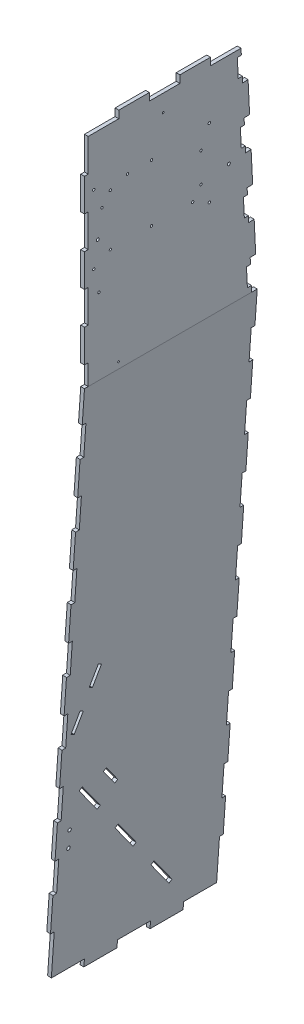
SolidWorks part; units mm, degrees
ref_plane "Front Plane" through (0, 0, 0) normal (0, 0, 1) x (1, 0, 0)
ref_plane "Top Plane" through (0, 0, 0) normal (0, 1, 0) x (1, 0, 0)
ref_plane "Right Plane" through (0, 0, 0) normal (1, 0, 0) x (0, 0, -1)
sketch "Sketch1" plane through (0, 0, 0) normal (0, 0, 1) x (1, 0, 0)
  line L0 (-215.8818, 2052.32) -> (-215.8818, 1463.04)
  line L1 (-215.8818, 1463.04) -> (-316.0886, 20.32)
  line L2 (-316.0886, 20.32) -> (-317.5, 0)
  line L4 (-215.8818, 2052.32) -> (-215.8818, 2072.64)
  line L6 (-215.8818, 2072.64) -> (-205.7153, 2072.64)
  line L7 (-205.7153, 2072.64) -> (-205.7153, 1463.04)
  line L8 (-205.7153, 1463.04) -> (-307.3335, 0)
  line L9 (-317.5, 0) -> (-307.3335, 0)
  line L10 (-371.5407, 0) -> (-280.9748, 0) construction
  line L13 (-371.5407, 20.32) -> (-280.9748, 20.32) construction
  line L15 (-205.7153, 1463.04) -> (205.7153, 1463.04) construction
  point P23 (-305.9221, 20.32)
  dimension "D1" = 307.3335
extrude "Boss-Extrude1" add sketch "Sketch1" against normal blind 469.9
sketch "Sketch2" plane through (-315.9757, 21.9467, 0) normal (-0.9976, 0.0693, 0) x (0, 0, 1)
  line L35 (0, 1355.6785) -> (0, 0.1049)
  line L37 (-234.95, 1444.5652) -> (-234.95, -21.9996) construction
  line L40 (-10.16, 0.1049) -> (0, 0.1049)
  line L43 (-10.16, 0.1049) -> (-10.16, -21.9996)
  line L46 (0, 1272.0274) -> (-10.16, 1272.0274)
  line L47 (-10.16, 1355.6785) -> (-10.16, 1272.0274)
  line L48 (0, 1355.6785) -> (-10.16, 1355.6785)
  line L49 (0, 1177.9051) -> (-10.16, 1177.9051)
  line L50 (-10.16, 1177.9051) -> (-10.16, 1094.2274)
  line L51 (0, 1094.2274) -> (-10.16, 1094.2274)
  line L52 (0, 916.4274) -> (-10.16, 916.4274)
  line L53 (-10.16, 1000.1317) -> (-10.16, 916.4274)
  line L54 (0, 1000.1317) -> (-10.16, 1000.1317)
  line L55 (0, 822.3583) -> (-10.16, 822.3583)
  line L56 (0, 738.6274) -> (-10.16, 738.6274)
  line L57 (-10.16, 822.3583) -> (-10.16, 738.6274)
  line L58 (0, 644.5849) -> (-10.16, 644.5849)
  line L59 (-10.16, 644.5849) -> (-10.16, 560.8274)
  line L60 (0, 560.8274) -> (-10.16, 560.8274)
  line L61 (0, 466.8115) -> (-10.16, 466.8115)
  line L62 (-10.16, 466.8115) -> (-10.16, 383.0274)
  line L63 (0, 383.0274) -> (-10.16, 383.0274)
  line L64 (0, 289.0381) -> (-10.16, 289.0381)
  line L65 (-10.16, 289.0381) -> (-10.16, 205.2274)
  line L66 (0, 205.2274) -> (-10.16, 205.2274)
  line L67 (0, 111.2647) -> (-10.16, 111.2647)
  line L68 (-10.16, 111.2647) -> (-10.16, 0.1049)
  line L69 (0, 0.1049) -> (-10.16, 0.1049)
  line L70 (-10.16, -21.9996) -> (0, -21.9996)
  line L71 (0, 0.1049) -> (0, -21.9996)
  line L72 (-469.9, 1444.5652) -> (0, 1444.5652) construction
  line L73 (-469.9, -21.9996) -> (0, -21.9996) construction
  line L74 (-469.9, 0.1049) -> (-469.9, -21.9996)
  line L75 (-459.74, -21.9996) -> (-469.9, -21.9996)
  line L76 (-469.9, 0.1049) -> (-459.74, 0.1049)
  line L77 (-459.74, 111.2647) -> (-459.74, 0.1049)
  line L78 (-469.9, 111.2647) -> (-459.74, 111.2647)
  line L79 (-469.9, 205.2274) -> (-459.74, 205.2274)
  line L80 (-459.74, 289.0381) -> (-459.74, 205.2274)
  line L81 (-469.9, 289.0381) -> (-459.74, 289.0381)
  line L82 (-469.9, 383.0274) -> (-459.74, 383.0274)
  line L83 (-459.74, 466.8115) -> (-459.74, 383.0274)
  line L84 (-469.9, 466.8115) -> (-459.74, 466.8115)
  line L85 (-469.9, 560.8274) -> (-459.74, 560.8274)
  line L86 (-459.74, 644.5849) -> (-459.74, 560.8274)
  line L87 (-469.9, 644.5849) -> (-459.74, 644.5849)
  line L88 (-459.74, 822.3583) -> (-459.74, 738.6274)
  line L89 (-469.9, 738.6274) -> (-459.74, 738.6274)
  line L90 (-469.9, 822.3583) -> (-459.74, 822.3583)
  line L91 (-469.9, 1000.1317) -> (-459.74, 1000.1317)
  line L92 (-459.74, 1000.1317) -> (-459.74, 916.4274)
  line L93 (-469.9, 916.4274) -> (-459.74, 916.4274)
  line L94 (-469.9, 1094.2274) -> (-459.74, 1094.2274)
  line L95 (-459.74, 1177.9051) -> (-459.74, 1094.2274)
  line L96 (-469.9, 1177.9051) -> (-459.74, 1177.9051)
  line L97 (-469.9, 1355.6785) -> (-459.74, 1355.6785)
  line L98 (-459.74, 1355.6785) -> (-459.74, 1272.0274)
  line L99 (-469.9, 1272.0274) -> (-459.74, 1272.0274)
  line L100 (-459.74, 0.1049) -> (-459.74, -21.9996)
  line L101 (-459.74, 0.1049) -> (-469.9, 0.1049)
  line L102 (-469.9, 1355.6785) -> (-469.9, 0.1049)
  line L103 (-469.9, 1444.5652) -> (-469.9, -21.9996) construction
  line L104 (-459.74, 205.2274) -> (-469.9, 205.2274) construction
  line M1 (0, -21.9996) -> (0, 1444.5652)
  line M3 (-469.9, 1444.5652) -> (-469.9, -21.9996)
  line M4 (-469.9, -21.9996) -> (0, -21.9996)
extrude "Cut-Extrude1" cut sketch "Sketch2" against normal blind 10.16 contours L66 L35 L64 L65 | L69 L67 L68 M1 | L60 L35 L58 L59 | L63 L35 L61 L62 | L55 L57 L56 L35 | L35 L54 L53 L52 | L51 L35 L49 L50 | L35 L48 L47 L46 | L40 L43 M4 M1 | L100 L76 M3 M4 | L78 L76 L77 M3 | L81 L79 L80 M3 | L84 L82 L83 M3 | L87 L85 L86 M3 | L90 L89 L88 M3 | L93 L92 L91 M3 | L96 L94 L95 M3 | L99 L98 L97 M3 region at (-224.9388, 1332.6419, -464.82) region at (-237.2577, 1155.2825, -464.82) region at (-249.5765, 977.9231, -464.82) region at (-261.8953, 800.5637, -464.82) region at (-274.2142, 623.2043, -464.82) region at (-286.533, 445.8449, -464.82) region at (-298.8518, 268.4855, -464.82) region at (-316.7342, 11.0257, -464.82) region at (-312.1173, 77.4977, -5.08) region at (-298.8518, 268.4855, -5.08) region at (-286.533, 445.8449, -5.08) region at (-274.2142, 623.2043, -5.08) region at (-261.8953, 800.5637, -5.08) region at (-249.5765, 977.9231, -5.08) region at (-237.2577, 1155.2825, -5.08) region at (-224.9388, 1332.6419, -5.08) region at (-316.7342, 11.0257, -5.08) region at (-312.1173, 77.4977, -464.82)
sketch "Sketch3" plane through (-215.8818, 0, 0) normal (-1, 0, 0) x (0, 0, 1)
  line L0 (0, 2052.32) -> (-10.16, 2052.32) construction
  line L1 (0, 1963.42) -> (-10.16, 1963.42) construction
  line L2 (-10.16, 2052.32) -> (-10.16, 1963.42) construction
  line L3 (0, 1874.52) -> (-10.16, 1874.52) construction
  line L4 (0, 1463.04) -> (0, 2072.64)
  line L5 (0, 2072.64) -> (-469.9, 2072.64)
  line L6 (-469.9, 2072.64) -> (-469.9, 1463.04)
  line L8 (0, 1463.04) -> (0, 2072.64)
  line L9 (0, 2072.64) -> (-469.9, 2072.64)
  line L12 (0, 1785.62) -> (-10.16, 1785.62) construction
  line L13 (-10.16, 1874.52) -> (-10.16, 1785.62) construction
  line L14 (0, 1696.72) -> (-10.16, 1696.72) construction
  line L15 (0, 1607.82) -> (-10.16, 1607.82) construction
  line L16 (-10.16, 1696.72) -> (-10.16, 1607.82) construction
  line L17 (0, 1518.92) -> (-10.16, 1518.92) construction
  line L18 (-10.16, 1518.92) -> (-10.16, 1488.44) construction
  line L19 (0, 2052.32) -> (-10.16, 2052.32)
  line L20 (0, 1963.42) -> (-10.16, 1963.42)
  line L21 (-10.16, 2052.32) -> (-10.16, 1963.42)
  line L22 (0, 1874.52) -> (-10.16, 1874.52)
  line L23 (0, 1785.62) -> (-10.16, 1785.62)
  line L24 (-10.16, 1874.52) -> (-10.16, 1785.62)
  line L25 (0, 1696.72) -> (-10.16, 1696.72)
  line L26 (0, 1607.82) -> (-10.16, 1607.82)
  line L27 (-10.16, 1696.72) -> (-10.16, 1607.82)
  line L28 (0, 1518.92) -> (-10.16, 1518.92)
  line L29 (-10.16, 1518.92) -> (-10.16, 1488.44)
  line L30 (0, 2052.32) -> (0, 1463.04)
  line L31 (-234.95, 1463.04) -> (-234.95, 2072.64) construction
  line L32 (-10.16, 2052.32) -> (0, 2052.32)
  line L33 (-10.16, 2052.32) -> (-10.16, 2072.64)
  line L34 (-10.16, 2072.64) -> (0, 2072.64)
  line L35 (0, 2052.32) -> (0, 2072.64)
  line L36 (-469.9, 1463.04) -> (-439.9, 2072.64)
  line L37 (-469.9, 1463.04) -> (-465.752, 1547.3282)
  line L38 (-469.9, 1463.04) -> (-454.9181, 1462.3027)
  line L39 (-465.752, 1547.3282) -> (-450.7701, 1546.5909)
  line L40 (-454.9181, 1462.3027) -> (-450.7701, 1546.5909)
  line L41 (-465.752, 1547.3282) -> (-450.7701, 1546.5909)
  line L42 (-465.752, 1547.3282) -> (-461.6039, 1631.6164)
  line L43 (-450.7701, 1546.5909) -> (-446.622, 1630.8791)
  line L44 (-461.6039, 1631.6164) -> (-446.622, 1630.8791)
  line L45 (-461.6039, 1631.6164) -> (-446.622, 1630.8791)
  line L46 (-461.6039, 1631.6164) -> (-457.4559, 1715.9046)
  line L47 (-446.622, 1630.8791) -> (-442.474, 1715.1673)
  line L48 (-457.4559, 1715.9046) -> (-442.474, 1715.1673)
  line L49 (-457.4559, 1715.9046) -> (-442.474, 1715.1673)
  line L50 (-457.4559, 1715.9046) -> (-453.3078, 1800.1927)
  line L51 (-442.474, 1715.1673) -> (-438.326, 1799.4554)
  line L52 (-453.3078, 1800.1927) -> (-438.326, 1799.4554)
  line L53 (-453.3078, 1800.1927) -> (-438.326, 1799.4554)
  line L54 (-10.16, 1488.44) -> (-10.16, 1463.04)
  line L56 (-453.3078, 1800.1927) -> (-449.1598, 1884.4809)
  line L57 (-438.326, 1799.4554) -> (-434.1779, 1883.7436)
  line L58 (-449.1598, 1884.4809) -> (-434.1779, 1883.7436)
  line L59 (-449.1598, 1884.4809) -> (-434.1779, 1883.7436)
  line L60 (-449.1598, 1884.4809) -> (-445.0118, 1968.7691)
  line L61 (-434.1779, 1883.7436) -> (-430.0299, 1968.0318)
  line L62 (-445.0118, 1968.7691) -> (-430.0299, 1968.0318)
  line L63 (-10.16, 2052.32) -> (-469.9, 2052.32) construction
  line L64 (-469.9, 2072.64) -> (-469.9, 1463.04) construction
  line L65 (-445.0118, 1968.7691) -> (-430.0299, 1968.0318)
  line L66 (-445.0118, 1968.7691) -> (-440.8637, 2053.0573)
  line L67 (-430.0299, 1968.0318) -> (-425.8818, 2052.32)
  line L68 (-440.8637, 2053.0573) -> (-425.8818, 2052.32)
  line L69 (-425.8818, 2052.32) -> (-440.9, 2052.32)
  line L70 (-440.8637, 2053.0573) -> (-425.8818, 2052.32)
  line L71 (-440.8637, 2053.0573) -> (-439.4854, 2081.0647)
  line L72 (-425.8818, 2052.32) -> (-424.5035, 2080.3274)
  line L73 (-439.4854, 2081.0647) -> (-424.5035, 2080.3274)
  line L74 (-469.9, 1463.04) -> (0, 1463.04) construction
  line L78 (-469.9, 1463.04) -> (0, 1463.04)
  line L79 (-469.9, 1463.04) -> (0, 1463.04)
  line M7 (0, 1463.04) -> (0, 2072.64)
  line M8 (0, 2072.64) -> (-469.9, 2072.64)
  line M9 (-469.9, 2072.64) -> (-469.9, 1463.04)
  line M10 (-469.9, 1463.04) -> (0, 1463.04)
  dimension "D2" = 30
  dimension "D3" = 15
  dimension "D1" = 0
extrude "Cut-Extrude2" cut sketch "Sketch3" against normal blind 12.7 contours M10 | L29 L54 L28 M10 M7 | L36 L66 M9 M8 | L48 L36 L44 L47 | L58 L36 L52 L57 | L67 L69 L36 L62 | L25 L27 L26 L8 | L22 L24 L23 L8 | L19 L21 L20 L8 | L33 L19 L8 M8 | L68 L72 L36 M8 | L69 L68 L66 region at (-215.8818, 1490.98, -5.08) region at (-215.8818, 1652.27, -5.08) region at (-215.8818, 1505, -460.337) region at (-215.8818, 1869.44, -459.9) region at (-215.8818, 1830.07, -5.08) region at (-215.8818, 1673.3918, -452.039) region at (-215.8818, 2062.6632, -432.8357) region at (-215.8818, 2007.87, -5.08) region at (-215.8818, 1841.9682, -443.7429) region at (-215.8818, 2052.5658, -435.8819) region at (-215.8818, 2062.48, -5.08) region at (-215.8818, 2010.36, -435.4449)
sketch "Sketch4" plane through (-215.8818, 0, 0) normal (-1, 0, 0) x (0, 0, 1)
  line L1 (-425.8818, 2072.64) -> (-342.7375, 2072.64)
  line L2 (-425.8818, 2072.64) -> (-425.8818, 2052.32)
  line L3 (-425.8818, 2052.32) -> (-342.7375, 2052.32)
  line L4 (-342.7375, 2072.64) -> (-342.7375, 2052.32)
  line L5 (-10.16, 2072.64) -> (-10.16, 1963.42) construction
  line L6 (-342.7375, 2072.64) -> (-259.5931, 2072.64)
  line L7 (-342.7375, 2072.64) -> (-342.7375, 2052.32)
  line L8 (-342.7375, 2052.32) -> (-259.5931, 2052.32)
  line L9 (-259.5931, 2072.64) -> (-259.5931, 2052.32)
  line L10 (-259.5931, 2072.64) -> (-176.4487, 2072.64)
  line L11 (-259.5931, 2072.64) -> (-259.5931, 2052.32)
  line L12 (-259.5931, 2052.32) -> (-176.4487, 2052.32)
  line L13 (-176.4487, 2072.64) -> (-176.4487, 2052.32)
  line L14 (-176.4487, 2072.64) -> (-93.3044, 2072.64)
  line L15 (-176.4487, 2072.64) -> (-176.4487, 2052.32)
  line L16 (-176.4487, 2052.32) -> (-93.3044, 2052.32)
  line L17 (-93.3044, 2072.64) -> (-93.3044, 2052.32)
  line L18 (-93.3044, 2072.64) -> (-10.16, 2072.64)
  line L19 (-93.3044, 2072.64) -> (-93.3044, 2052.32)
  line L20 (-93.3044, 2052.32) -> (-10.16, 2052.32)
  line L21 (-10.16, 2072.64) -> (-10.16, 2052.32)
  line L23 (-430.0299, 1968.0318) -> (-424.8818, 2072.64) construction
  line L24 (-424.8818, 2072.64) -> (-10.16, 2072.64) construction
  line M26 (-10.16, 1963.42) -> (-10.16, 2072.64)
  line M27 (-10.16, 2072.64) -> (-424.8818, 2072.64)
  dimension "D1" = 20.32
extrude "Cut-Extrude3" cut sketch "Sketch4" against normal blind 12.7 contours L4 L3 M27 | L13 L9 L12 M27 | L17 L20 M26 M27 region at (-215.8818, 2062.48, -384.3097) region at (-215.8818, 2062.48, -218.0209) region at (-215.8818, 2062.48, -51.7322)
sketch "Sketch5" plane through (-315.9757, 21.9467, 0) normal (-0.9976, 0.0693, 0) x (0, 0, 1)
  line L1 (-459.74, -21.9996) -> (-369.824, -21.9996)
  line L2 (-459.74, -21.9996) -> (-459.74, -1.6796)
  line L3 (-459.74, -1.6796) -> (-369.824, -1.6796)
  line L4 (-369.824, -21.9996) -> (-369.824, -1.6796)
  line L5 (-369.824, -21.9996) -> (-279.908, -21.9996)
  line L6 (-369.824, -21.9996) -> (-369.824, -1.6796)
  line L7 (-369.824, -1.6796) -> (-279.908, -1.6796)
  line L8 (-279.908, -21.9996) -> (-279.908, -1.6796)
  line L9 (-279.908, -21.9996) -> (-189.992, -21.9996)
  line L10 (-279.908, -21.9996) -> (-279.908, -1.6796)
  line L11 (-279.908, -1.6796) -> (-189.992, -1.6796)
  line L12 (-189.992, -21.9996) -> (-189.992, -1.6796)
  line L13 (-189.992, -21.9996) -> (-100.076, -21.9996)
  line L14 (-189.992, -21.9996) -> (-189.992, -1.6796)
  line L15 (-189.992, -1.6796) -> (-100.076, -1.6796)
  line L16 (-100.076, -21.9996) -> (-100.076, -1.6796)
  line L17 (-100.076, -21.9996) -> (-10.16, -21.9996)
  line L18 (-100.076, -21.9996) -> (-100.076, -1.6796)
  line L19 (-100.076, -1.6796) -> (-10.16, -1.6796)
  line L20 (-10.16, -21.9996) -> (-10.16, -1.6796)
  line L21 (-10.16, 111.2647) -> (-10.16, -21.9996) construction
  dimension "D1" = 20.32
extrude "Cut-Extrude4" cut sketch "Sketch5" against normal blind 12.7 contours L1 L4 L3 L2 | L9 L12 L11 L8 | L17 L20 L19 L18 L16 region at (-316.796, 10.1356, -414.782) region at (-316.796, 10.1356, -234.95) region at (-316.796, 10.1356, -55.118)
sketch "Sketch6" plane through (-315.9757, 21.9467, 0) normal (-0.9976, 0.0693, 0) x (0, 0, 1)
  line L0 (-217.3726, 211.9965) -> (-163.4402, 285.2141)
  line L1 (-325.2304, 65.5562) -> (-271.298, 138.7738)
  line L2 (-44.1085, 632.6765) -> (-22.5289, 586.4358) construction
  line L3 (-74.8989, 674.6188) -> (-65.6881, 678.9173) construction
  line L8 (-271.6486, 139.032) -> (-279.8219, 145.0526) construction
  line L56 (-87.2678, 725.158) -> (-65.6881, 678.9173) construction
  line L57 (-74.8989, 674.6188) -> (-96.4785, 720.8595) construction
  line L58 (-31.7396, 582.1373) -> (-22.5289, 586.4358) construction
  line L59 (-31.7396, 582.1373) -> (-53.3192, 628.3781) construction
  line L60 (-53.3192, 628.3781) -> (-44.1085, 632.6765) construction
  line L63 (-117.6881, 364.4573) -> (-63.7557, 437.6749) construction
  line L65 (-225.5528, 218.0222) -> (-171.6205, 291.2397) construction
  line L69 (-333.4176, 71.587) -> (-279.4852, 144.8046) construction
  line L70 (-109.5008, 358.4266) -> (-55.5685, 431.6442)
  line L71 (-44.1085, 632.6765) -> (-22.5289, 586.4358)
  line L72 (-74.8989, 674.6188) -> (-65.6881, 678.9173)
  line L73 (-87.2678, 725.158) -> (-65.6881, 678.9173)
  line L74 (-74.8989, 674.6188) -> (-96.4785, 720.8595)
  line L75 (-31.7396, 582.1373) -> (-22.5289, 586.4358)
  line L76 (-31.7396, 582.1373) -> (-53.3192, 628.3781)
  line L77 (-53.3192, 628.3781) -> (-44.1085, 632.6765)
  line L78 (-109.5008, 358.4266) -> (-117.6881, 364.4573)
  line L79 (-55.5685, 431.6442) -> (-63.7557, 437.6749)
  line L80 (-117.6881, 364.4573) -> (-63.7557, 437.6749)
  line L81 (-163.4402, 285.2141) -> (-171.6205, 291.2397)
  line L82 (-225.5528, 218.0222) -> (-171.6205, 291.2397)
  line L83 (-217.3726, 211.9965) -> (-225.5528, 218.0222)
  line L84 (-271.298, 138.7738) -> (-279.4852, 144.8046)
  line L85 (-325.2304, 65.5562) -> (-333.4176, 71.587)
  line L86 (-333.4176, 71.587) -> (-279.4852, 144.8046)
  line L87 (-87.2678, 725.158) -> (-96.4785, 720.8595)
  line L89 (-109.8514, 358.6848) -> (-118.0248, 364.7053) construction
  line L90 (-163.7838, 285.4672) -> (-171.9572, 291.4877) construction
  line L91 (-217.7162, 212.2496) -> (-225.8895, 218.2702) construction
  dimension "D1" = 10.16
sketch "Sketch8" plane through (-215.8818, 0, 0) normal (-1, 0, 0) x (0, 0, 1)
  circle A0 centre (-450.215, 1043.94) radius 9.525 construction
  circle A1 centre (-450.215, 1043.94) radius 9.525
sketch "Sketch13" plane through (-215.8818, 0, 0) normal (-1, 0, 0) x (0, 0, 1)
  line L0 (-413.556, 1633.6344) -> (-413.556, 1614.5844) construction
  line L1 (-270.8715, 1611.4094) -> (-270.8715, 1636.8094) construction
  line L2 (-413.556, 1624.1094) -> (-270.8715, 1624.1094) construction
  line L3 (-270.8715, 1624.1094) -> (-400.856, 1624.1094) construction
  line L4 (-270.8715, 1605.0594) -> (-400.856, 1605.0594) construction
  line L5 (-270.8715, 1643.1594) -> (-400.856, 1643.1594) construction
  line L6 (-416.7447, 2052.32) -> (-335.4278, 2052.32)
  line L7 (-422.8907, 1968.0316) -> (-416.7447, 2052.32)
  circle A0 centre (-25.2465, 1731.87) radius 3.175
  circle A1 centre (-70.409, 1755.42) radius 3.175
  circle A2 centre (-182.409, 1755.42) radius 3.175
  circle A3 centre (-25.2465, 1918.97) radius 3.175
  circle A4 centre (-47.789, 1865.42) radius 3.175
  circle A5 centre (-182.409, 1910.42) radius 3.175
  circle A6 centre (-117.079, 1910.42) radius 3.175
  circle A7 centre (-70.409, 1895.42) radius 3.175
  circle A8 centre (-317.029, 1865.42) radius 3.175
  circle A9 centre (-294.409, 1755.42) radius 3.175
  circle A10 centre (-317.029, 1785.42) radius 3.175
  circle A11 centre (-339.5715, 1731.87) radius 3.175
  circle A12 centre (-339.5715, 1918.97) radius 3.175
  arc A13 (-270.8715, 1605.0594) -> (-270.8715, 1643.1594) centre (-270.8715, 1624.1094) ccw construction
  arc A14 (-400.856, 1643.1594) -> (-400.856, 1605.0594) centre (-400.856, 1624.1094) ccw construction
  point P34 (-335.8637, 1624.1094)
  point P42 (-425.8818, 2052.32)
  dimension "D1" = 12.7
  dimension "D2" = 19.05
extrude "Cut-Extrude8" cut sketch "Sketch13" against normal through all contours L5 A14 L4 A13 | A11 | A10 | A9 | A2 | A1 | A0 | A4 | A7 | A6 | A3 | A5 | A8 | A12 | L0 A14 region at (-215.8818, 1731.87, -25.2465) region at (-215.8818, 1755.42, -70.409) region at (-215.8818, 1755.42, -182.409) region at (-215.8818, 1918.97, -25.2465) region at (-215.8818, 1865.42, -47.789) region at (-215.8818, 1910.42, -182.409) region at (-215.8818, 1910.42, -117.079) region at (-215.8818, 1895.42, -70.409) region at (-215.8818, 1865.42, -317.029) region at (-215.8818, 1755.42, -294.409) region at (-215.8818, 1785.42, -317.029) region at (-215.8818, 1731.87, -339.5715) region at (-215.8818, 1918.97, -339.5715)
sketch "Sketch17" plane through (-215.8818, 0, 0) normal (-1, 0, 0) x (0, 0, 1)
  line L0 (-130.4243, 1639.6605) -> (-120.5247, 1641.946)
  line L1 (-120.5247, 1641.946) -> (-107.584, 1585.8939)
  line L2 (-130.4243, 1639.6605) -> (-117.4836, 1583.6084)
  line L3 (-117.4836, 1583.6084) -> (-107.584, 1585.8939)
  line L4 (-104.543, 1527.5563) -> (-94.6434, 1529.8418)
  line L5 (-91.6023, 1471.5043) -> (-104.543, 1527.5563)
  line L6 (-91.6023, 1471.5043) -> (-81.7027, 1473.7898)
  line L7 (-81.7027, 1473.7898) -> (-94.6434, 1529.8418)
  line L10 (-94.6434, 1529.8418) -> (-120.5247, 1641.946) construction
  line L11 (-166.7373, 1842.1148) -> (-120.5247, 1641.946) construction
  line L12 (-91.6023, 1471.5043) -> (-130.4243, 1639.6605) construction
  line L13 (-130.4243, 1639.6605) -> (-176.6418, 1839.8508) construction
  line L14 (-173.9916, 1828.3716) -> (-164.0921, 1830.6571)
  line L15 (-164.0921, 1830.6571) -> (-154.8072, 1790.44)
  line L16 (-154.8072, 1790.44) -> (-164.7068, 1788.1545)
  line L17 (-164.7068, 1788.1545) -> (-173.9916, 1828.3716)
  point P11 (-425.8818, 2052.32)
  dimension "D1" = 152.4
  dimension "D2" = 41.275
sketch "Sketch20" plane through (-315.9757, 21.9467, 0) normal (-0.9976, 0.0693, 0) x (0, 0, 1)
  line L2 (-258.1103, 563.7707) -> (-10.16, 315.8204)
  line L8 (-10.16, 110.1771) -> (-10.16, -1.6796)
  line L9 (-10.16, 466.8115) -> (-10.16, 383.0274) construction
  line L10 (-13.335, 290.1376) -> (-13.335, 359.9876)
  line L11 (-13.335, 290.1376) -> (-48.26, 290.1376)
  line L12 (-13.335, 359.9876) -> (-48.26, 359.9876)
  line L13 (-48.26, 290.1376) -> (-48.26, 359.9876)
  line L32 (-120.9293, 445.7124) -> (-154.8235, 399.6982)
  line L33 (-120.9293, 445.7124) -> (-128.5983, 451.3614)
  line L34 (-154.8235, 399.6982) -> (-162.4926, 405.3473)
  line L35 (-128.5983, 451.3614) -> (-162.4926, 405.3473)
  line L39 (-137.8764, 422.7053) -> (43.6586, 288.9858) construction
  line L40 (-35.56, 332.8883) -> (-35.56, 361.687) construction
  line L41 (-10.16, 466.8115) -> (-10.16, 383.0274)
  circle A0 centre (-35.56, 347.2876) radius 4.7625
  circle A2 centre (-35.56, 302.8376) radius 4.7625
  point P11 (-10.16, -1.6796)
  point P57 (-35.56, 341.2204)
  dimension "D9" = 44.45
  dimension "D15" = 9.525
  dimension "D3" = 3.175
  dimension "D4" = 12.7
  dimension "D6" = 317.5
  dimension "D7" = 12.7
  dimension "D8" = 12.7
  dimension "D25" = 34.925
extrude "Cut-Extrude10" cut sketch "Sketch20" against normal through all contours A2 | L2 A0 | L2 A0 | L2 L35 L34 L32 | L33 L35 L2 L32 region at (-285.2619, 464.1454, -128.5379) region at (-286.8509, 441.2683, -145.572) region at (-291.908, 368.4591, -35.5004) region at (-292.1316, 365.2395, -38.7278) region at (-294.992, 324.0565, -35.56)
sketch "Sketch22" [suppressed] plane through (-315.9757, 21.9467, 0) normal (-0.9976, 0.0693, 0) x (0, 0, 1)
  line L3 (-138.6114, 421.183) -> (-138.6114, 431.343)
  line L4 (-138.6114, 431.343) -> (-202.8371, 431.343)
  line L5 (-138.6114, 421.183) -> (-202.8371, 421.183)
  line L6 (-202.8371, 421.183) -> (-202.8371, 431.343)
  line L7 (-267.0629, 421.183) -> (-267.0629, 431.343)
  line L8 (-267.0629, 431.343) -> (-331.2886, 431.343)
  line L9 (-267.0629, 421.183) -> (-331.2886, 421.183)
  line L10 (-331.2886, 421.183) -> (-331.2886, 431.343)
  line L11 (-395.5143, 421.183) -> (-395.5143, 431.343)
  line L12 (-395.5143, 421.183) -> (-459.74, 421.183)
  line L13 (-395.5143, 431.343) -> (-459.74, 431.343)
  line L15 (-459.74, 421.183) -> (-459.74, 431.343)
  line L16 (-100.076, -1.6796) -> (-10.16, -1.6796) construction
  line L17 (-10.16, 111.2647) -> (-10.16, -1.6796) construction
  line L18 (-100.076, -1.6796) -> (-10.16, -1.6796)
  line L19 (-10.16, 111.2647) -> (-10.16, -1.6796)
  point P0 (-10.16, -1.6796)
sketch "Sketch23" plane through (-315.9757, 21.9467, 0) normal (-0.9976, 0.0693, 0) x (0, 0, 1)
  line L2 (-450.215, 1024.4555) -> (-396.5689, 1024.4555) construction
  line L3 (-437.515, 986.3555) -> (-437.515, 1062.5555) construction
  circle A0 centre (-437.515, 986.3555) radius 3.175
  circle A1 centre (-421.64, 1024.4555) radius 3.175
  circle A2 centre (-437.515, 1062.5555) radius 3.175
  point P21 (-437.515, 1024.4555)
  dimension "D1" = 6.35
  dimension "D2" = 28.575
  dimension "D3" = 76.2
  dimension "D4" = 12.7
sketch "Sketch24" plane through (-215.8818, 0, 0) normal (-1, 0, 0) x (0, 0, 1)
  line L0 (-10.16, 1696.72) -> (-10.16, 1607.82) construction
  line L1 (0, 1696.72) -> (-10.16, 1696.72) construction
  circle A0 centre (-39.3138, 1670.4542) radius 18 construction
  circle A1 centre (-39.3138, 1670.4542) radius 18 construction
  circle A2 centre (-39.3137, 1670.4542) radius 3.175
  dimension "D1" = 6.35
  dimension "D2" = 29.1537
  dimension "D3" = 26.2658
extrude "Cut-Extrude12" cut sketch "Sketch24" against normal blind 12.7
sketch "Sketch26" plane through (-215.8818, 0, 0) normal (-1, 0, 0) x (0, 0, 1)
  line L4 (-74.8989, 694.9441) -> (-65.6881, 699.2322)
  line L5 (-65.6881, 699.2322) -> (-87.2678, 745.3618)
  line L6 (-87.2678, 745.3618) -> (-96.4785, 741.0737)
  line L7 (-96.4785, 741.0737) -> (-74.8989, 694.9441)
  line L8 (-74.8989, 694.9441) -> (-65.6881, 699.2322)
  line L9 (-65.6881, 699.2322) -> (-87.2678, 745.3618)
  line L10 (-87.2678, 745.3618) -> (-96.4785, 741.0737)
  line L11 (-96.4785, 741.0737) -> (-74.8989, 694.9441)
  line L12 (-22.5289, 606.973) -> (-44.1085, 653.1026)
  line L13 (-31.7396, 602.6849) -> (-22.5289, 606.973)
  line L14 (-53.3192, 648.8145) -> (-31.7396, 602.6849)
  line L15 (-44.1085, 653.1026) -> (-53.3192, 648.8145)
  line L16 (-22.5289, 606.973) -> (-44.1085, 653.1026)
  line L17 (-31.7396, 602.6849) -> (-22.5289, 606.973)
  line L18 (-53.3192, 648.8145) -> (-31.7396, 602.6849)
  line L19 (-44.1085, 653.1026) -> (-53.3192, 648.8145)
  line L20 (-117.6881, 385.5281) -> (-109.5008, 379.5118)
  line L21 (-63.7557, 458.5697) -> (-117.6881, 385.5281)
  line L22 (-55.5685, 452.5534) -> (-63.7557, 458.5697)
  line L23 (-109.5008, 379.5118) -> (-55.5685, 452.5534)
  line L24 (-117.6881, 385.5281) -> (-109.5008, 379.5118)
  line L25 (-63.7557, 458.5697) -> (-117.6881, 385.5281)
  line L26 (-55.5685, 452.5534) -> (-63.7557, 458.5697)
  line L27 (-109.5008, 379.5118) -> (-55.5685, 452.5534)
  line L28 (-325.2304, 87.3454) -> (-271.298, 160.387)
  line L29 (-271.298, 160.387) -> (-279.4852, 166.4032)
  line L30 (-279.4852, 166.4032) -> (-333.4176, 93.3616)
  line L31 (-333.4176, 93.3616) -> (-325.2304, 87.3454)
  line L32 (-325.2304, 87.3454) -> (-271.298, 160.387)
  line L33 (-271.298, 160.387) -> (-279.4852, 166.4032)
  line L34 (-279.4852, 166.4032) -> (-333.4176, 93.3616)
  line L35 (-333.4176, 93.3616) -> (-325.2304, 87.3454)
  line L36 (-217.3726, 233.4337) -> (-163.4402, 306.4753)
  line L37 (-163.4402, 306.4753) -> (-171.6205, 312.4864)
  line L38 (-171.6205, 312.4864) -> (-225.5528, 239.4448)
  line L39 (-225.5528, 239.4448) -> (-217.3726, 233.4337)
  line L40 (-217.3726, 233.4337) -> (-163.4402, 306.4753)
  line L41 (-163.4402, 306.4753) -> (-171.6205, 312.4864)
  line L42 (-171.6205, 312.4864) -> (-225.5528, 239.4448)
  line L43 (-225.5528, 239.4448) -> (-217.3726, 233.4337)
  dimension "D1" = 0
  dimension "D2" = 0
  dimension "D3" = 0
  dimension "D4" = 0
  dimension "D5" = 0
extrude "Cut-Extrude13" cut sketch "Sketch26" along normal through all both and the other way through all contours L24 L27 L26 L25 | L42 L43 L40 L41 | L16 L19 L18 L17 | L8 L9 L10 L11 | L34 L35 L32 L33 region at (-215.8818, 419.0407, -86.6283) region at (-215.8818, 272.9601, -194.4965)
sketch "Sketch28" plane through (0, 0, 0) normal (0, -1, 0) x (1, 0, 0)
  line L0 (-317.5, -369.824) -> (-307.3335, -369.824) construction
  line L1 (-307.3335, -369.824) -> (-307.3335, -279.908) construction
  line L2 (-307.3335, -279.908) -> (-317.5, -279.908) construction
  line L3 (-317.5, -279.908) -> (-317.5, -369.824) construction
  line L4 (-317.5, -189.992) -> (-307.3335, -189.992) construction
  line L5 (-307.3335, -189.992) -> (-307.3335, -100.076) construction
  line L6 (-307.3335, -100.076) -> (-317.5, -100.076) construction
  line L7 (-317.5, -100.076) -> (-317.5, -189.992) construction
  line L8 (-317.5, -369.824) -> (-307.3335, -369.824)
  line L9 (-307.3335, -369.824) -> (-307.3335, -279.908)
  line L10 (-307.3335, -279.908) -> (-317.5, -279.908)
  line L11 (-317.5, -279.908) -> (-317.5, -369.824)
  line L12 (-317.5, -189.992) -> (-307.3335, -189.992)
  line L13 (-307.3335, -189.992) -> (-307.3335, -100.076)
  line L14 (-307.3335, -100.076) -> (-317.5, -100.076)
  line L15 (-317.5, -100.076) -> (-317.5, -189.992)
sketch "Sketch29" plane through (-215.8818, 0, 0) normal (-1, 0, 0) x (0, 0, 1)
  line L0 (-404.8818, 1463.04) -> (-454.8818, 1463.04)
  line L1 (-454.8818, 1463.04) -> (-452.4242, 1512.9796)
  line L2 (-454.8818, 1463.04) -> (-450.7701, 1546.5909) construction
  circle A0 centre (-454.8818, 1463.04) radius 50
  dimension "D1" = 100
extrude "Cut-Extrude15" [suppressed] cut sketch "Sketch29" against normal through all both contours L0 A0 L1
sketch "Sketch30" plane through (-205.7153, 0, 0) normal (1, 0, 0) x (0, 0, -1)
  line L0 (10.16, 1785.62) -> (10.16, 1874.52) construction
  line L1 (10.16, 1785.62) -> (0, 1785.62) construction
  circle A0 centre (36.16, 1796.1325) radius 4
  circle A1 centre (392.66, 1796.1325) radius 4
  dimension "D1" = 8
  dimension "D2" = 26
  dimension "D4" = 356.5
  dimension "D5" = 8
  dimension "D3" = 10.5125
extrude "Cut-Extrude16" cut sketch "Sketch30" against normal blind 18
sketch "Sketch31" plane through (-205.7153, 0, 0) normal (1, 0, 0) x (0, 0, -1)
  circle A0 centre (92.6788, 1480.159) radius 2.3813
  circle A1 centre (214.0961, 2006.0752) radius 2.3813
  dimension "D1" = 4.7625
  dimension "D2" = 4.7625
extrude "Cut-Extrude17" cut sketch "Sketch31" against normal blind 20
sketch "Sketch32" plane through (-215.8818, 0, 0) normal (-1, 0, 0) x (0, 0, 1)
  line L0 (-454.8818, 1463.04) -> (-450.7701, 1546.5909) construction
  line L1 (-454.8818, 1463.04) -> (-450.7701, 1546.5909) construction
  line L2 (-443.973, 1462.5031) -> (-439.8613, 1546.054) construction
  line L3 (-446.622, 1630.8791) -> (-442.474, 1715.1673) construction
  line L4 (-446.622, 1630.8791) -> (-442.474, 1715.1673) construction
  line L5 (-438.326, 1799.4554) -> (-434.1779, 1883.7436) construction
  line L6 (-438.326, 1799.4554) -> (-434.1779, 1883.7436) construction
  line L7 (-430.0299, 1968.0318) -> (-425.8818, 2052.32) construction
  line L8 (-430.0299, 1968.0318) -> (-425.8818, 2052.32) construction
  line L9 (-435.7133, 1630.3422) -> (-431.5652, 1714.6304) construction
  line L10 (-427.4172, 1798.9186) -> (-423.2691, 1883.2068) construction
  line L11 (-419.1211, 1967.495) -> (-414.973, 2051.7831) construction
  line L12 (-427.9559, 2010.1759) -> (-417.0471, 2009.6391) construction
  line L13 (-436.2519, 1841.5995) -> (-425.3432, 1841.0627) construction
  line L14 (-444.548, 1673.0232) -> (-433.6392, 1672.4863) construction
  line L15 (-452.826, 1504.8154) -> (-441.9172, 1504.2786) construction
  line L16 (-418.2956, 1984.2698) -> (-415.7986, 2035.0084)
  line L17 (-426.5916, 1815.6934) -> (-424.0947, 1866.432)
  line L18 (-434.8877, 1647.117) -> (-432.3907, 1697.8556)
  line L19 (-443.1657, 1478.9093) -> (-440.6687, 1529.6479)
  line L20 (-415.7986, 2035.0084) -> (-426.7074, 2035.5452)
  line L21 (-418.2956, 1984.2698) -> (-429.2044, 1984.8066)
  line L22 (-426.7074, 2035.5452) -> (-429.2044, 1984.8066)
  line L23 (-424.0947, 1866.432) -> (-435.0035, 1866.9688)
  line L24 (-426.5916, 1815.6934) -> (-437.5004, 1816.2302)
  line L25 (-432.3907, 1697.8556) -> (-443.2995, 1698.3925)
  line L26 (-434.8877, 1647.117) -> (-445.7965, 1647.6539)
  line L27 (-440.6687, 1529.6479) -> (-451.5775, 1530.1847)
  line L28 (-443.1657, 1478.9093) -> (-454.0745, 1479.4461)
  line L29 (-454.0745, 1479.4461) -> (-451.5775, 1530.1847)
  line L30 (-443.2995, 1698.3925) -> (-445.7965, 1647.6539)
  line L31 (-435.0035, 1866.9688) -> (-437.5004, 1816.2302)
  point P23 (-444.548, 1673.0232)
  point P27 (-425.3432, 1841.0627)
  point P31 (-417.0471, 2009.6391)
  point P33 (-433.6392, 1672.4863)
  point P36 (-441.9172, 1504.2786)
  dimension "D5" = 50.8
  dimension "D1" = 10.922
  dimension "D2" = 10.922
  dimension "D3" = 10.922
  dimension "D4" = 10.922
extrude "Cut-Extrude18" cut sketch "Sketch32" against normal through all both and the other way through all
